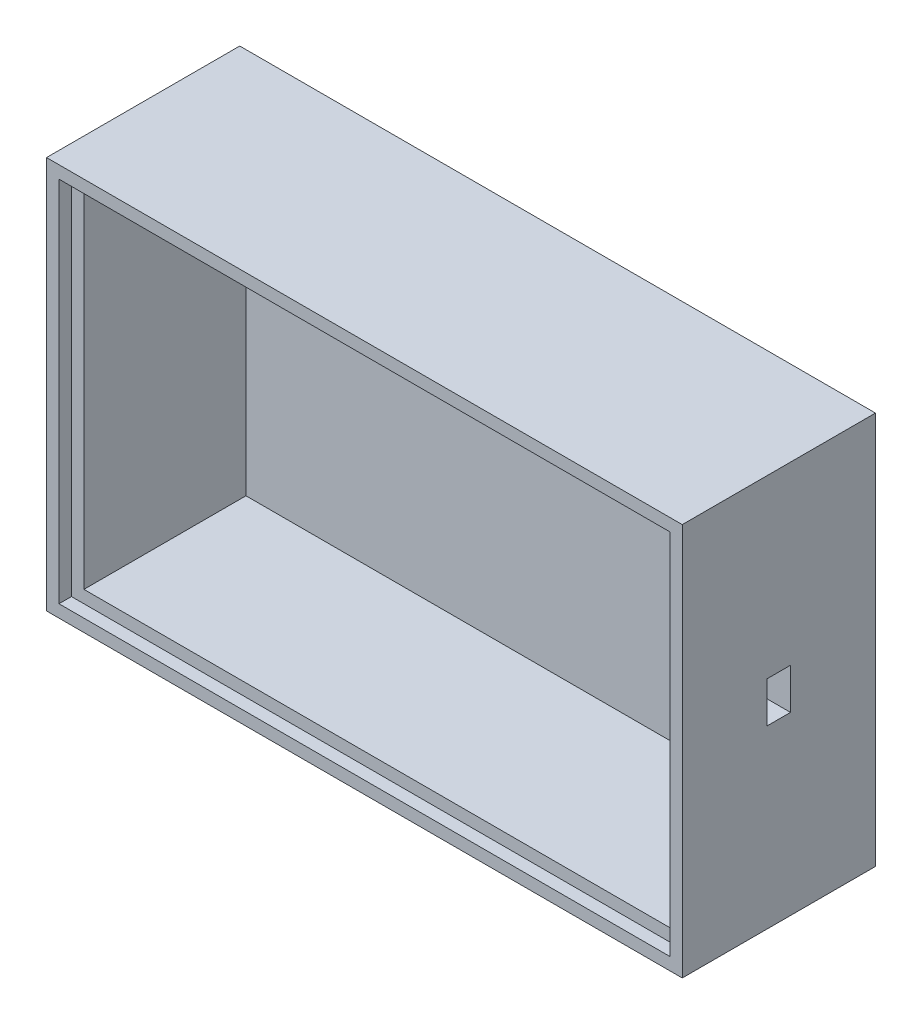
SolidWorks part; units mm, degrees
ref_plane "Přední rovina" through (0, 0, 0) normal (0, 0, 1) x (1, 0, 0)
ref_plane "Horní rovina" through (0, 0, 0) normal (0, 1, 0) x (1, 0, 0)
ref_plane "Pravá rovina" through (0, 0, 0) normal (1, 0, 0) x (0, 0, -1)
sketch "Skica1" plane through (0, 0, 0) normal (0, 0, 1) x (1, 0, 0)
  line L1 (0, 0) -> (98, 0)
  line L2 (0, 0) -> (0, 59)
  line L3 (0, 59) -> (98, 59)
  line L4 (98, 0) -> (98, 59)
  line L5 (-2, 61) -> (100, 61)
  line L6 (-2, 61) -> (-2, -2)
  line L7 (-2, -2) -> (100, -2)
  line L8 (100, 61) -> (100, -2)
  line L9 (2, 57) -> (96, 57)
  line L10 (2, 57) -> (2, 2)
  line L11 (2, 2) -> (96, 2)
  line L12 (96, 57) -> (96, 2)
  dimension "D1" = 102
  dimension "D2" = 63
  dimension "D3" = 2
  dimension "D4" = 2
  dimension "D5" = 2
  dimension "D6" = 2
  dimension "D7" = 2
  dimension "D8" = 2
  dimension "D9" = 2
  dimension "D10" = 2
  dimension "D11" = 55
  dimension "D12" = 94
extrude "Přidat vysunutím1" add sketch "Skica1" along normal blind 3 contours L6 L7 L8 L5
extrude "Přidat vysunutím2" add sketch "Skica1<4>" along normal blind 31 contours L8 L5 L6 L7 L4 L1 L2 L3 region at (49, 59.8011, 0)
sketch "Skica1<4>" plane through (0, 0, 0) normal (0, 0, 1) x (1, 0, 0) same geometry as "Skica1"
extrude "Přidat vysunutím3" add sketch "Skica1<5>" along normal blind 29 contours L1 L4 L3 L2 L9 L12 L11 L10 region at (1.1439, 29.5, 0)
sketch "Skica1<5>" plane through (0, 0, 0) normal (0, 0, 1) x (1, 0, 0) same geometry as "Skica1"
sketch "Skica2" plane through (100, 0, 0) normal (1, 0, 0) x (0, 0, -1)
  line L0 (-15.5, 61) -> (-15.5, -2) construction
  line L1 (-17.365, 26.225) -> (-13.635, 26.225)
  line L2 (-17.365, 26.225) -> (-17.365, 32.775)
  line L3 (-17.365, 32.775) -> (-13.635, 32.775)
  line L4 (-13.635, 26.225) -> (-13.635, 32.775)
  line L5 (-17.365, 26.225) -> (-13.635, 32.775) construction
  line L6 (-17.365, 32.775) -> (-13.635, 26.225) construction
  line L7 (-31, 61) -> (0, 61) construction
  line L8 (-31, -2) -> (0, -2) construction
  line L9 (-31, 29.5) -> (0, 29.5) construction
  line L10 (-31, 61) -> (-31, -2) construction
  line L11 (0, 61) -> (0, -2) construction
  point P0 (-15.5, 29.5)
  point P17 (-15.5, 29.5)
  dimension "D1" = 6.55
  dimension "D2" = 3.73
extrude "Odebrat vysunutím1" cut sketch "Skica2" against normal up to surface (4 mm away) up to face at (96, 29.5, 16)
